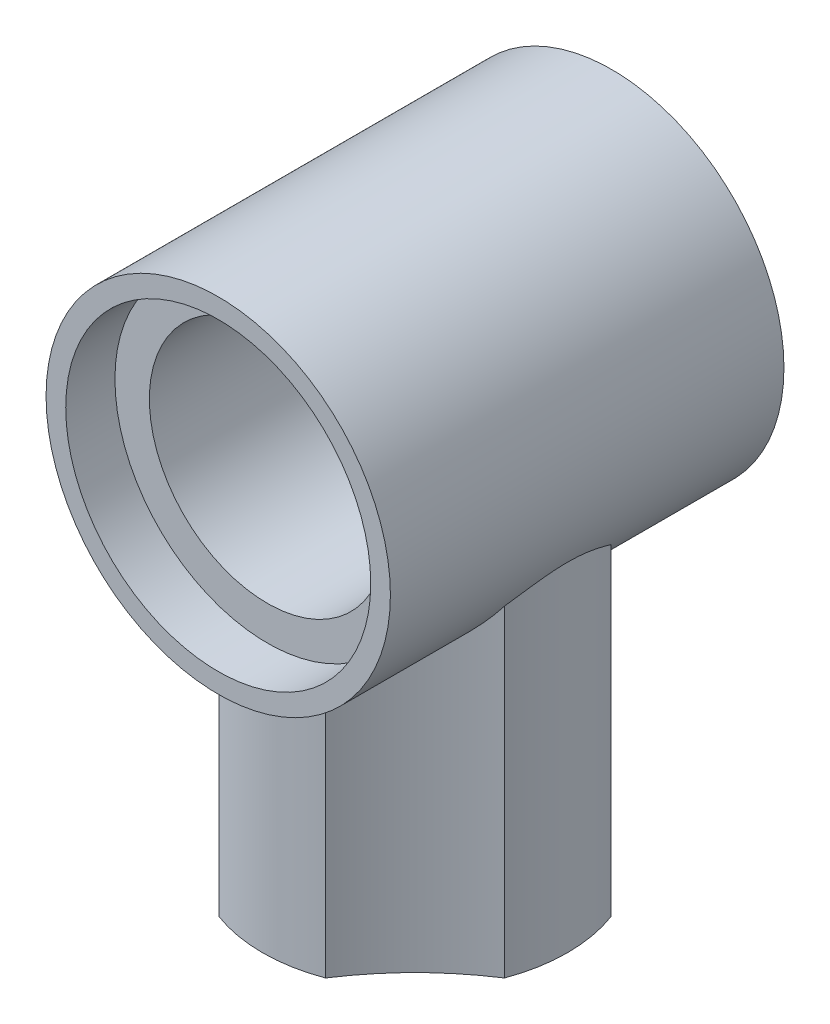
SolidWorks part; units mm, degrees
ref_plane "Front Plane" through (0, 0, 0) normal (0, 0, 1) x (1, 0, 0)
ref_plane "Top Plane" through (0, 0, 0) normal (0, 1, 0) x (1, 0, 0)
ref_plane "Right Plane" through (0, 0, 0) normal (1, 0, 0) x (0, 0, -1)
sketch "Sketch2" plane through (0, 0, 0) normal (0, 1, 0) x (1, 0, 0)
  line L0 (-1.085, -1.085) -> (-1.085, -2.9039)
  line L2 (-1.085, 2.9039) -> (-1.085, 1.085)
  line L4 (1.085, 2.9039) -> (1.085, 1.085)
  line L5 (-1.085, 2.9039) -> (1.085, -2.9039) construction
  line L6 (-1.085, -2.9039) -> (1.085, 2.9039) construction
  line L7 (-2.9039, 1.085) -> (-1.085, 1.085)
  line L9 (-2.9039, -1.085) -> (-1.085, -1.085)
  line L11 (-2.9039, 1.085) -> (2.9039, -1.085) construction
  line L12 (-2.9039, -1.085) -> (2.9039, 1.085) construction
  line L13 (1.085, 1.085) -> (2.9039, 1.085)
  line L14 (1.085, -1.085) -> (1.085, -2.9039)
  line L15 (1.085, -1.085) -> (2.9039, -1.085)
  arc A0 (-2.9039, 1.085) -> (-2.9039, -1.085) centre (0, 0) ccw
  arc A1 (1.085, 2.9039) -> (-1.085, 2.9039) centre (0, 0) ccw
  arc A2 (2.9039, -1.085) -> (2.9039, 1.085) centre (0, 0) ccw
  arc A3 (-1.085, -2.9039) -> (1.085, -2.9039) centre (0, 0) ccw
  dimension "D1" = 6.2
  dimension "D2" = 2.17
  dimension "D3" = 2.17
extrude "Boss-Extrude1" add sketch "Sketch2" along normal blind 7
fillet "Fillet1" radius 6.2 1 edges at (-1.085, 3.5, -1.085)
fillet "Fillet2" radius 6.2 1 edges at (1.085, 3.5, -1.085)
fillet "Fillet3" radius 6.2 1 edges at (1.085, 3.5, 1.085)
fillet "Fillet4" radius 6.2 1 edges at (-1.085, 3.5, 1.085)
sketch "Sketch4" plane through (0, 0, 0) normal (0, -1, 0) x (1, 0, 0)
  line L0 (0.84, 0.84) -> (0.84, 2.2482)
  line L2 (0.84, -2.2482) -> (0.84, -0.84)
  line L4 (-0.84, -2.2482) -> (-0.84, -0.84)
  line L5 (0.84, -2.2482) -> (-0.84, 2.2482) construction
  line L6 (0.84, 2.2482) -> (-0.84, -2.2482) construction
  line L7 (2.2482, -0.84) -> (0.84, -0.84)
  line L9 (2.2482, 0.84) -> (0.84, 0.84)
  line L11 (2.2482, -0.84) -> (-2.2482, 0.84) construction
  line L12 (2.2482, 0.84) -> (-2.2482, -0.84) construction
  line L13 (-0.84, -0.84) -> (-2.2482, -0.84)
  line L14 (-0.84, 0.84) -> (-0.84, 2.2482)
  line L15 (-0.84, 0.84) -> (-2.2482, 0.84)
  arc A0 (2.2482, -0.84) -> (2.2482, 0.84) centre (0, 0) ccw
  arc A1 (-0.84, -2.2482) -> (0.84, -2.2482) centre (0, 0) ccw
  arc A2 (-2.2482, 0.84) -> (-2.2482, -0.84) centre (0, 0) ccw
  arc A3 (0.84, 2.2482) -> (-0.84, 2.2482) centre (0, 0) ccw
  dimension "D1" = 4.8
  dimension "D2" = 1.68
  dimension "D3" = 1.68
extrude "Cut-Extrude1" cut sketch "Sketch4" against normal blind 5
sketch "Sketch5" plane through (0, 0, 0) normal (0, 0, 1) x (1, 0, 0)
  circle A2 centre (0, 8.5) radius 3.5
extrude "Boss-Extrude2" add sketch "Sketch5" along normal mid plane 8
sketch "Sketch9" plane through (0, 0, 4) normal (0, 0, 1) x (1, 0, 0)
  circle A0 centre (0, 8.5) radius 2.4
  dimension "D1" = 4.8
extrude "Cut-Extrude2" cut sketch "Sketch9" against normal through all
sketch "Sketch10" plane through (0, 0, 4) normal (0, 0, 1) x (1, 0, 0)
  circle A0 centre (0, 8.5) radius 3.1
  dimension "D1" = 6.2
extrude "Cut-Extrude3" cut sketch "Sketch10" against normal blind 1
mirror "Mirror1" about plane through (0, 0, 0) normal (0, 0, 1) of "Cut-Extrude3"
fillet "Fillet5" radius 0.4 1 edges at (0.84, 2.5, 0.84)
fillet "Fillet6" radius 0.4 1 edges at (-0.84, 2.5, 0.84)
fillet "Fillet7" radius 0.4 1 edges at (-0.84, 2.5, -0.84)
fillet "Fillet8" radius 0.4 1 edges at (0.84, 2.5, -0.84)
fillet "Fillet9" radius 0.1 1 edges at (-0.84, 2.5, 2.2482)
fillet "Fillet10" radius 0.1 1 edges at (0.84, 2.5, 2.2482)
fillet "Fillet11" radius 0.1 1 edges at (-2.2482, 2.5, -0.84)
fillet "Fillet12" radius 0.1 1 edges at (-2.2482, 2.5, 0.84)
fillet "Fillet13" radius 0.1 1 edges at (2.2482, 2.5, 0.84)
fillet "Fillet14" radius 0.1 1 edges at (2.2482, 2.5, -0.84)
fillet "Fillet15" radius 0.1 1 edges at (-0.84, 2.5, -2.2482)
fillet "Fillet16" radius 0.1 1 edges at (0.84, 2.5, -2.2482)
